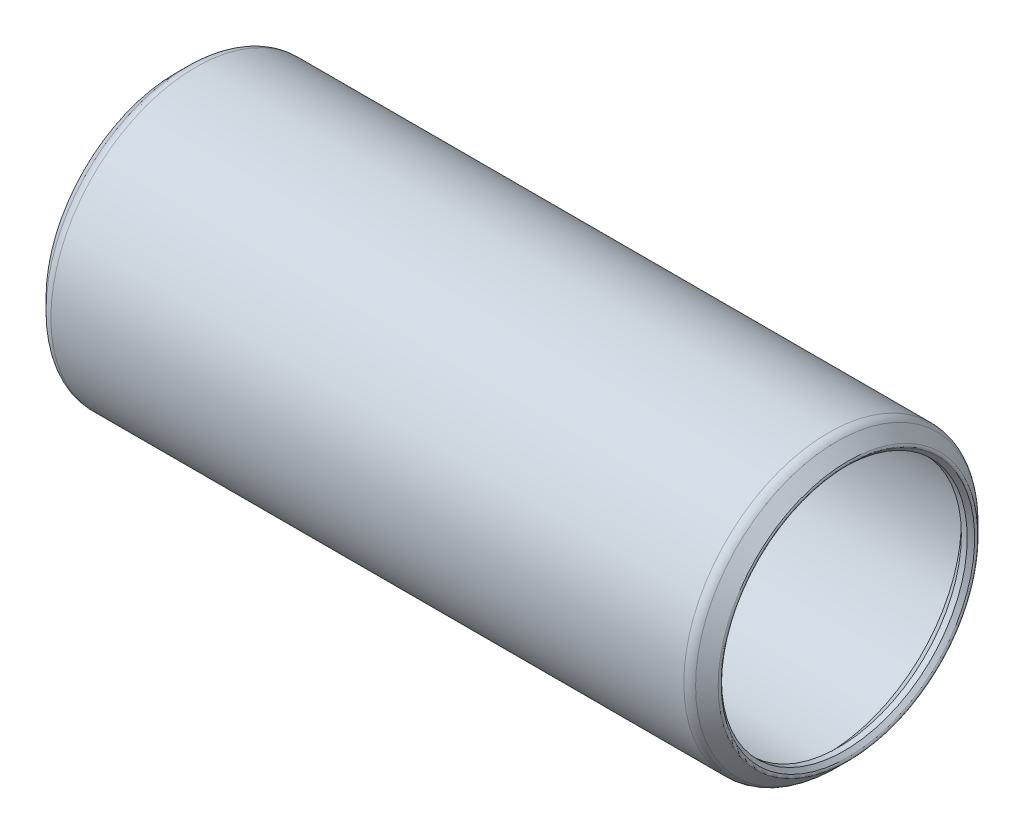
SolidWorks part; units mm, degrees
material "AISI 304"
ref_plane "Front Plane" through (0, 0, 0) normal (0, 0, 1) x (1, 0, 0)
ref_plane "Top Plane" through (0, 0, 0) normal (0, 1, 0) x (1, 0, 0)
ref_plane "Right Plane" through (0, 0, 0) normal (1, 0, 0) x (0, 0, -1)
ref_plane "Plane1" through (35.2552, 0, 0) normal (1, 0, 0) x (0, 0, -1)
sketch "Sketch1" plane through (0, 0, 0) normal (0, 0, 1) x (1, 0, 0)
  line L0 (-0.518, 6.8362) -> (-0.3175, 6.6357)
  line L1 (-0.3175, 6.6357) -> (0, 6.6357)
  line L2 (0, 6.6357) -> (0.635, 7.2707)
  line L3 (0.635, 7.2707) -> (34.6202, 7.2707)
  line L4 (34.6202, 7.2707) -> (35.2552, 6.6357)
  line L5 (35.2552, 6.6357) -> (35.5727, 6.6357)
  line L6 (35.5727, 6.6357) -> (35.7732, 6.8362)
  line L7 (35.7732, 7.0158) -> (35.1645, 7.6245)
  line L8 (34.7155, 7.8105) -> (0.5397, 7.8105)
  line L9 (0.0907, 7.6245) -> (-0.518, 7.0158)
  line L10 (35.2552, 0) -> (0, 0) construction
  arc A0 (-0.518, 7.0158) -> (-0.518, 6.8362) centre (-0.4282, 6.926) ccw
  arc A1 (35.7732, 6.8362) -> (35.7732, 7.0158) centre (35.6834, 6.926) ccw
  arc A2 (35.1645, 7.6245) -> (34.7155, 7.8105) centre (34.7155, 7.1755) ccw
  arc A3 (0.5397, 7.8105) -> (0.0907, 7.6245) centre (0.5397, 7.1755) ccw
revolve "Revolve1" add sketch "Sketch1" angle 360 about L10 reverse direction yes
ref_plane "Plane2" through (17.6276, 0, 0) normal (1, 0, 0) x (0, 0, -1)
ref_plane "cp1 XY" through (17.6276, 0, 0) normal (1, 0, 0) x (0, 0, -1)
ref_plane "cp1 XZ" through (0, 7.8105, 0) normal (0, -1, 0) x (-1, 0, 0)
ref_plane "cp1 YZ" through (0, 0, 0) normal (0, 0, -1) x (-1, 0, 0)
ref_axis "cp1 X" through (17.6276, 7.8105, 80.9) along (0, 0, -1)
ref_axis "cp1 Y" through (17.6276, -50, 0) along (0, 1, 0)
ref_axis "cp1 Z" through (80.9, 7.8105, 0) along (-1, 0, 0)
sketch3d "cp1"
  point P0 (17.6276, 7.8105, 0)
ref_plane "cp2 XY" through (17.6276, 0, 0) normal (1, 0, 0) x (0, 0, -1)
ref_plane "cp2 XZ" through (0, 0, 0) normal (0, -1, 0) x (-1, 0, 0)
ref_plane "cp2 YZ" through (0, 0, -7.8105) normal (0, 0, -1) x (-1, 0, 0)
ref_axis "cp2 X" through (17.6276, 0, 80.9) along (0, 0, -1)
ref_axis "cp2 Y" through (17.6276, -50, -7.8105) along (0, 1, 0)
ref_axis "cp2 Z" through (80.9, 0, -7.8105) along (-1, 0, 0)
sketch3d "cp2"
  point P0 (17.6276, 0, -7.8105)
ref_plane "cp3 XY" through (17.6276, 0, 0) normal (1, 0, 0) x (0, 0, -1)
ref_plane "cp3 XZ" through (0, -7.8105, 0) normal (0, -1, 0) x (-1, 0, 0)
ref_plane "cp3 YZ" through (0, 0, 0) normal (0, 0, -1) x (-1, 0, 0)
ref_axis "cp3 X" through (17.6276, -7.8105, 80.9) along (0, 0, -1)
ref_axis "cp3 Y" through (17.6276, -50, 0) along (0, 1, 0)
ref_axis "cp3 Z" through (80.9, -7.8105, 0) along (-1, 0, 0)
sketch3d "cp3"
  point P0 (17.6276, -7.8105, 0)
ref_plane "cp4 XY" through (17.6276, 0, 0) normal (1, 0, 0) x (0, 0, -1)
ref_plane "cp4 XZ" through (0, 0, 0) normal (0, -1, 0) x (-1, 0, 0)
ref_plane "cp4 YZ" through (0, 0, 7.8105) normal (0, 0, -1) x (-1, 0, 0)
ref_axis "cp4 X" through (17.6276, 0, 80.9) along (0, 0, -1)
ref_axis "cp4 Y" through (17.6276, -50, 7.8105) along (0, 1, 0)
ref_axis "cp4 Z" through (80.9, 0, 7.8105) along (-1, 0, 0)
sketch3d "cp4"
  point P0 (17.6276, 0, 7.8105)
ref_plane "tube_front XY" through (0, 0, 0) normal (1, 0, 0) x (0, 0, -1)
ref_plane "tube_front XZ" through (0, 0, 0) normal (0, -1, 0) x (-1, 0, 0)
ref_plane "tube_front YZ" through (0, 0, 0) normal (0, 0, -1) x (-1, 0, 0)
ref_axis "tube_front X" through (0, 0, 80.9) along (0, 0, -1)
ref_axis "tube_front Y" through (0, -50, 0) along (0, 1, 0)
ref_axis "tube_front Z" through (80.9, 0, 0) along (-1, 0, 0)
sketch3d "tube_front"
  point P0 (0, 0, 0)
ref_plane "tube_rear XY" through (35.2552, 0, 0) normal (1, 0, 0) x (0, 0, -1)
ref_plane "tube_rear XZ" through (0, 0, 0) normal (0, -1, 0) x (-1, 0, 0)
ref_plane "tube_rear YZ" through (0, 0, 0) normal (0, 0, -1) x (-1, 0, 0)
ref_axis "tube_rear X" through (35.2552, 0, 80.9) along (0, 0, -1)
ref_axis "tube_rear Y" through (35.2552, -50, 0) along (0, 1, 0)
ref_axis "tube_rear Z" through (80.9, 0, 0) along (-1, 0, 0)
sketch3d "tube_rear"
  point P0 (35.2552, 0, 0)
